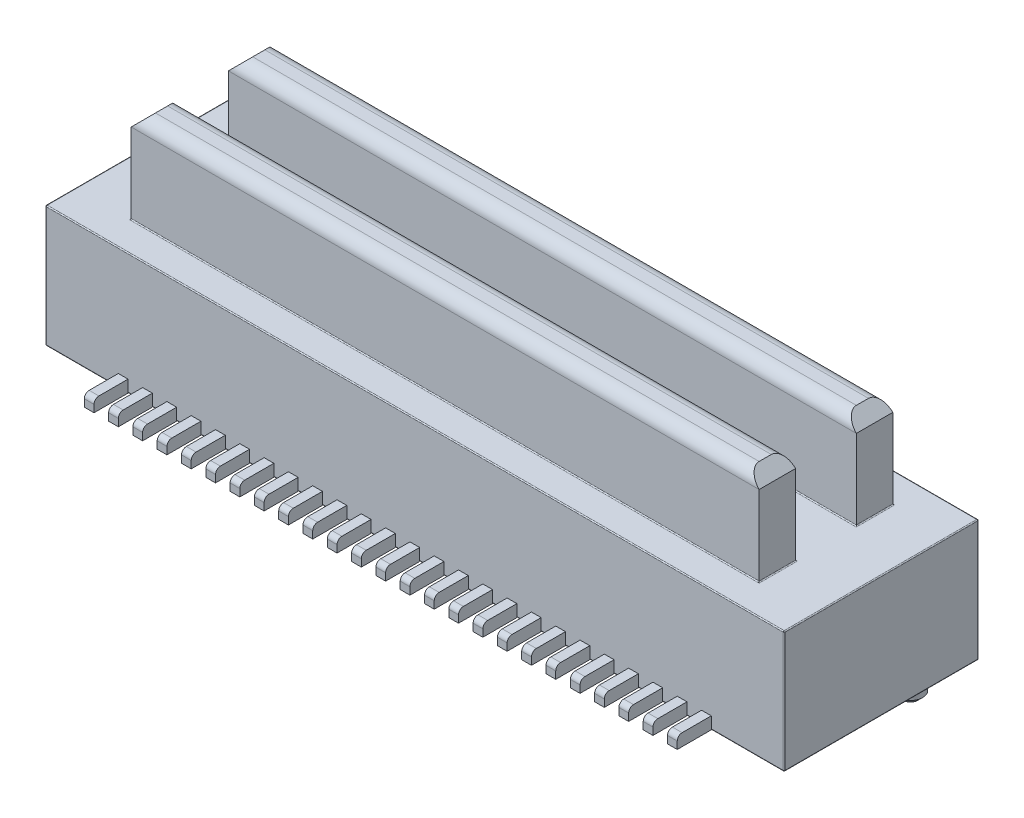
SolidWorks part; units mm, degrees
ref_plane "Front Plane" through (0, 0, 0) normal (0, 0, 1) x (1, 0, 0)
ref_plane "Top Plane" through (0, 0, 0) normal (0, 1, 0) x (1, 0, 0)
ref_plane "Right Plane" through (0, 0, 0) normal (1, 0, 0) x (0, 0, -1)
sketch "Sketch1" plane through (0, 0, 0) normal (0, 1, 0) x (1, 0, 0)
  line L0 (-6.95, 1.25) -> (6.95, 1.25) construction
  line L1 (7.6, 2) -> (-7.6, 2)
  line L2 (7.6, 2) -> (7.6, -2)
  line L3 (7.6, -2) -> (-7.6, -2)
  line L4 (-7.6, 2) -> (-7.6, -2)
  line L5 (7.6, 2) -> (-7.6, -2) construction
  line L6 (7.6, -2) -> (-7.6, 2) construction
  line L7 (-7.6, 0) -> (7.6, 0) construction
  line L8 (-6.1, 2.7) -> (-5.9, 2.7)
  line L9 (-6.1, 2.7) -> (-6.1, 1.2)
  line L10 (-6.1, 1.2) -> (-5.9, 1.2)
  line L11 (-5.9, 2.7) -> (-5.9, 1.2)
  line L12 (0, 2) -> (0, -2) construction
  line L13 (-5.6, 2.7) -> (-5.6, 1.2)
  line L14 (-5.6, 2.7) -> (-5.4, 2.7)
  line L15 (-5.4, 2.7) -> (-5.4, 1.2)
  line L16 (-5.6, 1.2) -> (-5.4, 1.2)
  line L17 (-5.1, 2.7) -> (-5.1, 1.2)
  line L18 (-5.1, 2.7) -> (-4.9, 2.7)
  line L19 (-4.9, 2.7) -> (-4.9, 1.2)
  line L20 (-5.1, 1.2) -> (-4.9, 1.2)
  line L21 (-4.6, 2.7) -> (-4.6, 1.2)
  line L22 (-4.6, 2.7) -> (-4.4, 2.7)
  line L23 (-4.4, 2.7) -> (-4.4, 1.2)
  line L24 (-4.6, 1.2) -> (-4.4, 1.2)
  line L25 (-4.1, 2.7) -> (-4.1, 1.2)
  line L26 (-4.1, 2.7) -> (-3.9, 2.7)
  line L27 (-3.9, 2.7) -> (-3.9, 1.2)
  line L28 (-4.1, 1.2) -> (-3.9, 1.2)
  line L29 (-3.6, 2.7) -> (-3.6, 1.2)
  line L30 (-3.6, 2.7) -> (-3.4, 2.7)
  line L31 (-3.4, 2.7) -> (-3.4, 1.2)
  line L32 (-3.6, 1.2) -> (-3.4, 1.2)
  line L33 (-3.1, 2.7) -> (-3.1, 1.2)
  line L34 (-3.1, 2.7) -> (-2.9, 2.7)
  line L35 (-2.9, 2.7) -> (-2.9, 1.2)
  line L36 (-3.1, 1.2) -> (-2.9, 1.2)
  line L37 (-2.6, 2.7) -> (-2.6, 1.2)
  line L38 (-2.6, 2.7) -> (-2.4, 2.7)
  line L39 (-2.4, 2.7) -> (-2.4, 1.2)
  line L40 (-2.6, 1.2) -> (-2.4, 1.2)
  line L41 (-2.1, 2.7) -> (-2.1, 1.2)
  line L42 (-2.1, 2.7) -> (-1.9, 2.7)
  line L43 (-1.9, 2.7) -> (-1.9, 1.2)
  line L44 (-2.1, 1.2) -> (-1.9, 1.2)
  line L45 (-1.6, 2.7) -> (-1.6, 1.2)
  line L46 (-1.6, 2.7) -> (-1.4, 2.7)
  line L47 (-1.4, 2.7) -> (-1.4, 1.2)
  line L48 (-1.6, 1.2) -> (-1.4, 1.2)
  line L49 (-1.1, 2.7) -> (-1.1, 1.2)
  line L50 (-1.1, 2.7) -> (-0.9, 2.7)
  line L51 (-0.9, 2.7) -> (-0.9, 1.2)
  line L52 (-1.1, 1.2) -> (-0.9, 1.2)
  line L53 (-0.6, 2.7) -> (-0.6, 1.2)
  line L54 (-0.6, 2.7) -> (-0.4, 2.7)
  line L55 (-0.4, 2.7) -> (-0.4, 1.2)
  line L56 (-0.6, 1.2) -> (-0.4, 1.2)
  line L57 (-0.1, 2.7) -> (-0.1, 1.2)
  line L58 (-0.1, 2.7) -> (0.1, 2.7)
  line L59 (0.1, 2.7) -> (0.1, 1.2)
  line L60 (-0.1, 1.2) -> (0.1, 1.2)
  line L61 (0.4, 2.7) -> (0.4, 1.2)
  line L62 (0.4, 2.7) -> (0.6, 2.7)
  line L63 (0.6, 2.7) -> (0.6, 1.2)
  line L64 (0.4, 1.2) -> (0.6, 1.2)
  line L65 (0.9, 2.7) -> (0.9, 1.2)
  line L66 (0.9, 2.7) -> (1.1, 2.7)
  line L67 (1.1, 2.7) -> (1.1, 1.2)
  line L68 (0.9, 1.2) -> (1.1, 1.2)
  line L69 (1.4, 2.7) -> (1.4, 1.2)
  line L70 (1.4, 2.7) -> (1.6, 2.7)
  line L71 (1.6, 2.7) -> (1.6, 1.2)
  line L72 (1.4, 1.2) -> (1.6, 1.2)
  line L73 (1.9, 2.7) -> (1.9, 1.2)
  line L74 (1.9, 2.7) -> (2.1, 2.7)
  line L75 (2.1, 2.7) -> (2.1, 1.2)
  line L76 (1.9, 1.2) -> (2.1, 1.2)
  line L77 (2.4, 2.7) -> (2.4, 1.2)
  line L78 (2.4, 2.7) -> (2.6, 2.7)
  line L79 (2.6, 2.7) -> (2.6, 1.2)
  line L80 (2.4, 1.2) -> (2.6, 1.2)
  line L81 (2.9, 2.7) -> (2.9, 1.2)
  line L82 (2.9, 2.7) -> (3.1, 2.7)
  line L83 (3.1, 2.7) -> (3.1, 1.2)
  line L84 (2.9, 1.2) -> (3.1, 1.2)
  line L85 (3.4, 2.7) -> (3.4, 1.2)
  line L86 (3.4, 2.7) -> (3.6, 2.7)
  line L87 (3.6, 2.7) -> (3.6, 1.2)
  line L88 (3.4, 1.2) -> (3.6, 1.2)
  line L89 (3.9, 2.7) -> (3.9, 1.2)
  line L90 (3.9, 2.7) -> (4.1, 2.7)
  line L91 (4.1, 2.7) -> (4.1, 1.2)
  line L92 (3.9, 1.2) -> (4.1, 1.2)
  line L93 (4.4, 2.7) -> (4.4, 1.2)
  line L94 (4.4, 2.7) -> (4.6, 2.7)
  line L95 (4.6, 2.7) -> (4.6, 1.2)
  line L96 (4.4, 1.2) -> (4.6, 1.2)
  line L97 (4.9, 2.7) -> (4.9, 1.2)
  line L98 (4.9, 2.7) -> (5.1, 2.7)
  line L99 (5.1, 2.7) -> (5.1, 1.2)
  line L100 (4.9, 1.2) -> (5.1, 1.2)
  line L101 (5.4, 2.7) -> (5.4, 1.2)
  line L102 (5.4, 2.7) -> (5.6, 2.7)
  line L103 (5.6, 2.7) -> (5.6, 1.2)
  line L104 (5.4, 1.2) -> (5.6, 1.2)
  line L105 (5.9, 2.7) -> (5.9, 1.2)
  line L106 (5.9, 2.7) -> (6.1, 2.7)
  line L107 (6.1, 2.7) -> (6.1, 1.2)
  line L108 (5.9, 1.2) -> (6.1, 1.2)
  line L109 (5.9, -2.7) -> (6.1, -2.7)
  line L110 (6.1, -2.7) -> (6.1, -1.2)
  line L111 (5.9, -1.2) -> (6.1, -1.2)
  line L112 (5.9, -2.7) -> (5.9, -1.2)
  line L113 (5.4, -2.7) -> (5.6, -2.7)
  line L114 (5.6, -2.7) -> (5.6, -1.2)
  line L115 (5.4, -1.2) -> (5.6, -1.2)
  line L116 (5.4, -2.7) -> (5.4, -1.2)
  line L117 (4.9, -2.7) -> (5.1, -2.7)
  line L118 (5.1, -2.7) -> (5.1, -1.2)
  line L119 (4.9, -1.2) -> (5.1, -1.2)
  line L120 (4.9, -2.7) -> (4.9, -1.2)
  line L121 (4.4, -2.7) -> (4.6, -2.7)
  line L122 (4.6, -2.7) -> (4.6, -1.2)
  line L123 (4.4, -1.2) -> (4.6, -1.2)
  line L124 (4.4, -2.7) -> (4.4, -1.2)
  line L125 (3.9, -2.7) -> (4.1, -2.7)
  line L126 (4.1, -2.7) -> (4.1, -1.2)
  line L127 (3.9, -1.2) -> (4.1, -1.2)
  line L128 (3.9, -2.7) -> (3.9, -1.2)
  line L129 (3.4, -2.7) -> (3.6, -2.7)
  line L130 (3.6, -2.7) -> (3.6, -1.2)
  line L131 (3.4, -1.2) -> (3.6, -1.2)
  line L132 (3.4, -2.7) -> (3.4, -1.2)
  line L133 (2.9, -2.7) -> (3.1, -2.7)
  line L134 (3.1, -2.7) -> (3.1, -1.2)
  line L135 (2.9, -1.2) -> (3.1, -1.2)
  line L136 (2.9, -2.7) -> (2.9, -1.2)
  line L137 (2.4, -2.7) -> (2.6, -2.7)
  line L138 (2.6, -2.7) -> (2.6, -1.2)
  line L139 (2.4, -1.2) -> (2.6, -1.2)
  line L140 (2.4, -2.7) -> (2.4, -1.2)
  line L141 (1.9, -2.7) -> (2.1, -2.7)
  line L142 (2.1, -2.7) -> (2.1, -1.2)
  line L143 (1.9, -1.2) -> (2.1, -1.2)
  line L144 (1.9, -2.7) -> (1.9, -1.2)
  line L145 (1.4, -2.7) -> (1.6, -2.7)
  line L146 (1.6, -2.7) -> (1.6, -1.2)
  line L147 (1.4, -1.2) -> (1.6, -1.2)
  line L148 (1.4, -2.7) -> (1.4, -1.2)
  line L149 (0.9, -2.7) -> (1.1, -2.7)
  line L150 (1.1, -2.7) -> (1.1, -1.2)
  line L151 (0.9, -1.2) -> (1.1, -1.2)
  line L152 (0.9, -2.7) -> (0.9, -1.2)
  line L153 (0.4, -2.7) -> (0.6, -2.7)
  line L154 (0.6, -2.7) -> (0.6, -1.2)
  line L155 (0.4, -1.2) -> (0.6, -1.2)
  line L156 (0.4, -2.7) -> (0.4, -1.2)
  line L157 (-0.1, -2.7) -> (0.1, -2.7)
  line L158 (0.1, -2.7) -> (0.1, -1.2)
  line L159 (-0.1, -1.2) -> (0.1, -1.2)
  line L160 (-0.1, -2.7) -> (-0.1, -1.2)
  line L161 (-0.6, -2.7) -> (-0.4, -2.7)
  line L162 (-0.4, -2.7) -> (-0.4, -1.2)
  line L163 (-0.6, -1.2) -> (-0.4, -1.2)
  line L164 (-0.6, -2.7) -> (-0.6, -1.2)
  line L165 (-1.1, -2.7) -> (-0.9, -2.7)
  line L166 (-0.9, -2.7) -> (-0.9, -1.2)
  line L167 (-1.1, -1.2) -> (-0.9, -1.2)
  line L168 (-1.1, -2.7) -> (-1.1, -1.2)
  line L169 (-1.6, -2.7) -> (-1.4, -2.7)
  line L170 (-1.4, -2.7) -> (-1.4, -1.2)
  line L171 (-1.6, -1.2) -> (-1.4, -1.2)
  line L172 (-1.6, -2.7) -> (-1.6, -1.2)
  line L173 (-2.1, -2.7) -> (-1.9, -2.7)
  line L174 (-1.9, -2.7) -> (-1.9, -1.2)
  line L175 (-2.1, -1.2) -> (-1.9, -1.2)
  line L176 (-2.1, -2.7) -> (-2.1, -1.2)
  line L177 (-2.6, -2.7) -> (-2.4, -2.7)
  line L178 (-2.4, -2.7) -> (-2.4, -1.2)
  line L179 (-2.6, -1.2) -> (-2.4, -1.2)
  line L180 (-2.6, -2.7) -> (-2.6, -1.2)
  line L181 (-3.1, -2.7) -> (-2.9, -2.7)
  line L182 (-2.9, -2.7) -> (-2.9, -1.2)
  line L183 (-3.1, -1.2) -> (-2.9, -1.2)
  line L184 (-3.1, -2.7) -> (-3.1, -1.2)
  line L185 (-3.6, -2.7) -> (-3.4, -2.7)
  line L186 (-3.4, -2.7) -> (-3.4, -1.2)
  line L187 (-3.6, -1.2) -> (-3.4, -1.2)
  line L188 (-3.6, -2.7) -> (-3.6, -1.2)
  line L189 (-4.1, -2.7) -> (-3.9, -2.7)
  line L190 (-3.9, -2.7) -> (-3.9, -1.2)
  line L191 (-4.1, -1.2) -> (-3.9, -1.2)
  line L192 (-4.1, -2.7) -> (-4.1, -1.2)
  line L193 (-4.6, -2.7) -> (-4.4, -2.7)
  line L194 (-4.4, -2.7) -> (-4.4, -1.2)
  line L195 (-4.6, -1.2) -> (-4.4, -1.2)
  line L196 (-4.6, -2.7) -> (-4.6, -1.2)
  line L197 (-5.1, -2.7) -> (-4.9, -2.7)
  line L198 (-4.9, -2.7) -> (-4.9, -1.2)
  line L199 (-5.1, -1.2) -> (-4.9, -1.2)
  line L200 (-5.1, -2.7) -> (-5.1, -1.2)
  line L201 (-5.6, -2.7) -> (-5.4, -2.7)
  line L202 (-5.4, -2.7) -> (-5.4, -1.2)
  line L203 (-5.6, -1.2) -> (-5.4, -1.2)
  line L204 (-5.6, -2.7) -> (-5.6, -1.2)
  line L205 (-6.1, -1.2) -> (-5.9, -1.2)
  line L206 (-5.9, -2.7) -> (-5.9, -1.2)
  line L207 (-6.1, -2.7) -> (-5.9, -2.7)
  line L208 (-6.1, -2.7) -> (-6.1, -1.2)
  circle A0 centre (-6.95, 1.25) radius 0.25
  circle A1 centre (6.95, 1.25) radius 0.25
  point P0 (0, 0)
  point P8 (0, 1.25)
  point P19 (-6, 2.7)
  point P20 (-5.5, 2.7)
  dimension "D5" = 0.5
  dimension "D1" = 13.9
  dimension "D2" = 15.2
  dimension "D3" = 4
  dimension "D4" = 1.25
  dimension "D6" = 0.2
  dimension "D7" = 1.2
  dimension "D8" = 1.5
  dimension "D9" = 6
  dimension "D11" = 0.5
  dimension "D10" = 25
extrude "Boss-Extrude1" add sketch "Sketch1" along normal blind 2.5 contours L3 L208 L205 L206 L204 L203 L202 L200 L199 L198 L196 L195 L194 L192 L191 L190 L188 L187 L186 L184 L183 L182 L180 L179 L178 L176 L175 L174 L172 L171 L170 L168 L167 L166 L164 L163 L162 L160 L159 | L208 L3 L206 L205 | L204 L3 L202 L203 | L200 L3 L198 L199 | L196 L3 L194 L195 | L192 L3 L190 L191 | L188 L3 L186 L187 | L184 L3 L182 L183 | L180 L3 L178 L179 | L176 L3 L174 L175 | L172 L3 L170 L171 | L168 L3 L166 L167 | L164 L3 L162 L163 | L160 L3 L158 L159 | L156 L3 L154 L155 | L152 L3 L150 L151 | L148 L3 L146 L147 | L144 L3 L142 L143 | L140 L3 L138 L139 | L136 L3 L134 L135 | L132 L3 L130 L131 | L128 L3 L126 L127 | L124 L3 L122 L123 | L120 L3 L118 L119 | L116 L3 L114 L115 | L112 L3 L110 L111 | A1 | A0 | L11 L1 L9 L10 | L13 L16 L15 L1 | L17 L20 L19 L1 | L21 L24 L23 L1 | L25 L28 L27 L1 | L29 L32 L31 L1 | L33 L36 L35 L1 | L37 L40 L39 L1 | L41 L44 L43 L1 | L45 L48 L47 L1 | L49 L52 L51 L1 | L53 L56 L55 L1 | L57 L60 L59 L1 | L61 L64 L63 L1 | L65 L68 L67 L1 | L69 L72 L71 L1 | L73 L76 L75 L1 | L77 L80 L79 L1 | L81 L84 L83 L1 | L85 L88 L87 L1 | L89 L92 L91 L1 | L93 L96 L95 L1 | L97 L100 L99 L1 | L101 L104 L103 L1 | L105 L108 L107 L1 region at (0, 0, 0.0094) region at (6, 0, -1.6) region at (6, 0, 1.6) region at (5.5, 0, -1.6) region at (5.5, 0, 1.6) region at (5, 0, -1.6) region at (5, 0, 1.6) region at (4.5, 0, -1.6) region at (4.5, 0, 1.6) region at (4, 0, -1.6) region at (4, 0, 1.6) region at (3.5, 0, -1.6) region at (3.5, 0, 1.6) region at (3, 0, -1.6) region at (3, 0, 1.6) region at (2.5, 0, -1.6) region at (2.5, 0, 1.6) region at (2, 0, -1.6) region at (2, 0, 1.6) region at (1.5, 0, -1.6) region at (1.5, 0, 1.6) region at (1, 0, -1.6) region at (1, 0, 1.6) region at (0.5, 0, -1.6) region at (0.5, 0, 1.6) region at (0, 0, -1.6) region at (0, 0, 1.6) region at (-0.5, 0, -1.6) region at (-0.5, 0, 1.6) region at (-1, 0, -1.6) region at (-1, 0, 1.6) region at (-1.5, 0, -1.6) region at (-1.5, 0, 1.6) region at (-2, 0, -1.6) region at (-2, 0, 1.6) region at (-2.5, 0, -1.6) region at (-2.5, 0, 1.6) region at (-3, 0, -1.6) region at (-3, 0, 1.6) region at (-3.5, 0, -1.6) region at (-3.5, 0, 1.6) region at (-4, 0, -1.6) region at (-4, 0, 1.6) region at (-4.5, 0, -1.6) region at (-4.5, 0, 1.6) region at (-5, 0, -1.6) region at (-5, 0, 1.6) region at (-5.5, 0, -1.6) region at (-5.5, 0, 1.6) region at (-6, 0, -1.6) region at (-6, 0, 1.6) region at (-6.95, 0, -1.25) region at (6.95, 0, -1.25)
sketch "Sketch2" plane through (0, 2.5, 0) normal (0, 1, 0) x (1, 0, 0)
  line L0 (0, -2) -> (0, 0) construction
  line L2 (7.6, -2) -> (-7.6, -2) construction
  line L3 (0, 0) -> (0, 2) construction
  line L4 (7.6, 2) -> (-7.6, 2) construction
  line L6 (-6.46, -0.625) -> (6.46, -0.625)
  line L7 (-6.46, -0.625) -> (-6.46, -1.375)
  line L8 (-6.46, -1.375) -> (6.46, -1.375)
  line L9 (6.46, -0.625) -> (6.46, -1.375)
  line L10 (-6.46, 1.375) -> (6.46, 1.375)
  line L11 (-6.46, 1.375) -> (-6.46, 0.625)
  line L12 (-6.46, 0.625) -> (6.46, 0.625)
  line L13 (6.46, 1.375) -> (6.46, 0.625)
  point P16 (-6.46, 1)
  point P17 (0, 1)
  point P18 (-6.46, -1)
  point P19 (0, -1)
  point P20 (0, 1.375)
  dimension "D1" = 0.75
  dimension "D2" = 12.92
extrude "Boss-Extrude2" add sketch "Sketch2" along normal blind 4.4 from surface starting at face at (0, 0, 0)
chamfer "Chamfer1" distance 0.25 angle 45 4 edges at (6.46, 4.4, 1) (6.46, 4.4, -1) (-6.46, 4.4, 1) (-6.46, 4.4, -1)
fillet "Fillet1" radius 0.25 4 edges at (0, 4.4, -1.375) (0, 4.4, -0.625) (0, 4.4, 0.625) (0, 4.4, 1.375)
fillet "Fillet2" radius 0.02 20 edges at (6.46, 2.5, -1) (0, 2.5, -0.625) (-6.46, 2.5, -1) (0, 2.5, -1.375) (6.46, 2.5, 1) (0, 2.5, 0.625) (0, 0, -2) (-7.6, 0, 0) (0, 0, 2) (7.6, 0, 0) (0, 2.5, -2) (-7.6, 2.5, 0) (0, 2.5, 2) (7.6, 2.5, 0) (7.6, 1.25, -2) (7.6, 1.25, 2) (-7.6, 1.25, 2) (-7.6, 1.25, -2) (-6.46, 2.5, 1) (0, 2.5, 1.375)
extrude "Boss-Extrude3" add sketch "Sketch1<3>" along normal blind 0.25 contours L208 L207 L206 L3 | L204 L201 L202 L3 | L200 L197 L198 L3 | L196 L193 L194 L3 | L192 L189 L190 L3 | L188 L185 L186 L3 | L184 L181 L182 L3 | L180 L177 L178 L3 | L176 L173 L174 L3 | L172 L169 L170 L3 | L168 L165 L166 L3 | L164 L161 L162 L3 | L160 L157 L158 L3 | L156 L153 L154 L3 | L152 L149 L150 L3 | L148 L145 L146 L3 | L144 L141 L142 L3 | L140 L137 L138 L3 | L136 L133 L134 L3 | L132 L129 L130 L3 | L128 L125 L126 L3 | L124 L121 L122 L3 | L120 L117 L118 L3 | L116 L113 L114 L3 | L112 L109 L110 L3 | L107 L106 L105 L1 | L103 L102 L101 L1 | L99 L98 L97 L1 | L95 L94 L93 L1 | L91 L90 L89 L1 | L87 L86 L85 L1 | L83 L82 L81 L1 | L79 L78 L77 L1 | L75 L74 L73 L1 | L71 L70 L69 L1 | L67 L66 L65 L1 | L63 L62 L61 L1 | L59 L58 L57 L1 | L55 L54 L53 L1 | L51 L50 L49 L1 | L47 L46 L45 L1 | L43 L42 L41 L1 | L39 L38 L37 L1 | L35 L34 L33 L1 | L31 L30 L29 L1 | L27 L26 L25 L1 | L23 L22 L21 L1 | L19 L18 L17 L1 | L15 L14 L13 L1 | L11 L8 L9 L1 region at (6, 0, -2.35) region at (6, 0, 2.35) region at (5.5, 0, -2.35) region at (5.5, 0, 2.35) region at (5, 0, -2.35) region at (5, 0, 2.35) region at (4.5, 0, -2.35) region at (4.5, 0, 2.35) region at (4, 0, -2.35) region at (4, 0, 2.35) region at (3.5, 0, -2.35) region at (3.5, 0, 2.35) region at (3, 0, -2.35) region at (3, 0, 2.35) region at (2.5, 0, -2.35) region at (2.5, 0, 2.35) region at (2, 0, -2.35) region at (2, 0, 2.35) region at (1.5, 0, -2.35) region at (1.5, 0, 2.35) region at (1, 0, -2.35) region at (1, 0, 2.35) region at (0.5, 0, -2.35) region at (0.5, 0, 2.35) region at (0, 0, -2.35) region at (0, 0, 2.35) region at (-0.5, 0, -2.35) region at (-0.5, 0, 2.35) region at (-1, 0, -2.35) region at (-1, 0, 2.35) region at (-1.5, 0, -2.35) region at (-1.5, 0, 2.35) region at (-2, 0, -2.35) region at (-2, 0, 2.35) region at (-2.5, 0, -2.35) region at (-2.5, 0, 2.35) region at (-3, 0, -2.35) region at (-3, 0, 2.35) region at (-3.5, 0, -2.35) region at (-3.5, 0, 2.35) region at (-4, 0, -2.35) region at (-4, 0, 2.35) region at (-4.5, 0, -2.35) region at (-4.5, 0, 2.35) region at (-5, 0, -2.35) region at (-5, 0, 2.35) region at (-5.5, 0, -2.35) region at (-5.5, 0, 2.35) region at (-6, 0, -2.35) region at (-6, 0, 2.35)
sketch "Sketch1<3>" plane through (0, 0, 0) normal (0, 1, 0) x (1, 0, 0) same geometry as "Sketch1"
fillet "Fillet3" radius 0.1 50 edges at (-4.5, 0.25, 2.7) (-4, 0.25, 2.7) (-3.5, 0.25, 2.7) (-3, 0.25, 2.7) (-2.5, 0.25, 2.7) (-2, 0.25, 2.7) (-1.5, 0.25, 2.7) (-1, 0.25, 2.7) (-5, 0.25, 2.7) (-0.5, 0.25, 2.7) (0, 0.25, 2.7) (0.5, 0.25, 2.7) (1, 0.25, 2.7) (1.5, 0.25, 2.7) (2, 0.25, 2.7) (2.5, 0.25, 2.7) (3, 0.25, 2.7) (3.5, 0.25, 2.7) (4, 0.25, 2.7) (4.5, 0.25, 2.7) (5, 0.25, 2.7) (5.5, 0.25, 2.7) (6, 0.25, 2.7) (-5.5, 0.25, 2.7) (-6, 0.25, 2.7) (-6, 0.25, -2.7) (-5.5, 0.25, -2.7) (-5, 0.25, -2.7) (-4.5, 0.25, -2.7) (-4, 0.25, -2.7) (-3.5, 0.25, -2.7) (-3, 0.25, -2.7) (-2.5, 0.25, -2.7) (-2, 0.25, -2.7) (-1.5, 0.25, -2.7) (-1, 0.25, -2.7) (-0.5, 0.25, -2.7) (0, 0.25, -2.7) (0.5, 0.25, -2.7) (1, 0.25, -2.7) (1.5, 0.25, -2.7) (2, 0.25, -2.7) (2.5, 0.25, -2.7) (3, 0.25, -2.7) (3.5, 0.25, -2.7) (4, 0.25, -2.7) (4.5, 0.25, -2.7) (5, 0.25, -2.7) (5.5, 0.25, -2.7) (6, 0.25, -2.7)
extrude "Boss-Extrude4" add sketch "Sketch1<4>" against normal blind 0.6 contours A1 | A0 region at (-6.95, 0, -1.25) region at (6.95, 0, -1.25)
sketch "Sketch1<4>" plane through (0, 0, 0) normal (0, 1, 0) x (1, 0, 0) same geometry as "Sketch1"
chamfer "Chamfer2" distance 0.1 angle 45 2 edges at (-6.95, -0.6, -1) (6.95, -0.6, -1)
